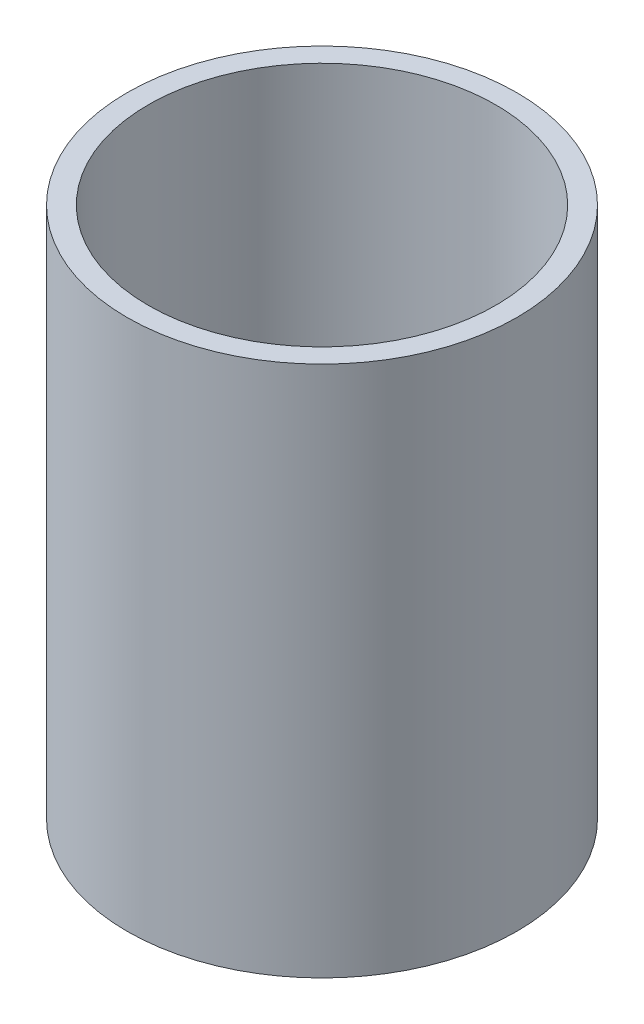
SolidWorks part; units mm, degrees
ref_plane "Front Plane" through (0, 0, 0) normal (0, 0, 1) x (1, 0, 0)
ref_plane "Top Plane" through (0, 0, 0) normal (0, 1, 0) x (1, 0, 0)
ref_plane "Right Plane" through (0, 0, 0) normal (1, 0, 0) x (0, 0, -1)
sketch "Sketch1" plane through (0, 0, 0) normal (0, 1, 0) x (1, 0, 0)
  circle A0 centre (0, 0) radius 57.5
  dimension "SLEEVE_OD" = 115
extrude "Boss-Extrude1" add sketch "Sketch1" along normal blind 156.9119
sketch "Sketch2" plane through (0, 0, 0) normal (0, 1, 0) x (1, 0, 0)
  circle A0 centre (0, 0) radius 51.2816
  dimension "BORE_D" = 102.5632
extrude "Cut-Extrude1" cut sketch "Sketch2" along normal through all
chamfer "Chamfer1" distance 3.9501 angle 45 rebuild error yes
